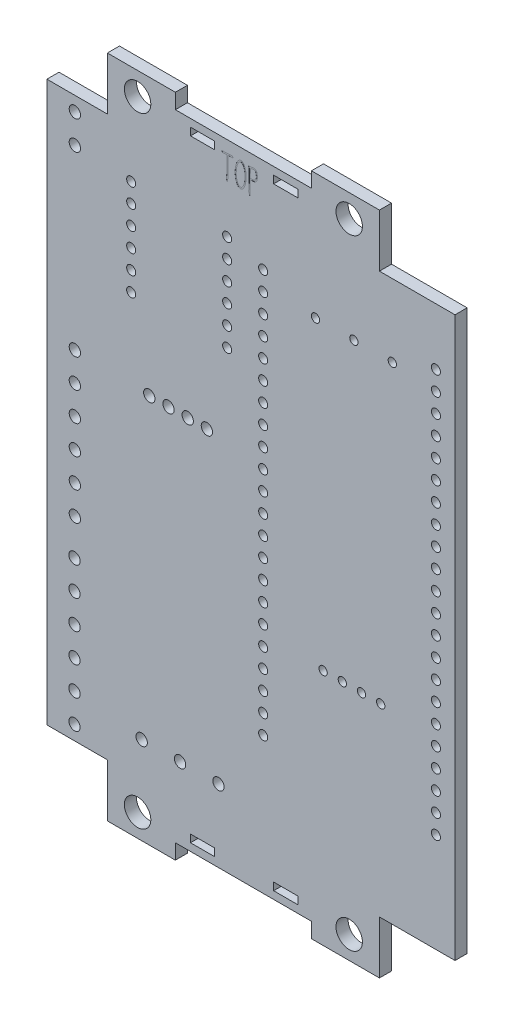
SolidWorks part; units mm, degrees
ref_plane "前视基准面" through (0, 0, 0) normal (0, 0, 1) x (1, 0, 0)
ref_plane "上视基准面" through (0, 0, 0) normal (0, 1, 0) x (1, 0, 0)
ref_plane "右视基准面" through (0, 0, 0) normal (1, 0, 0) x (0, 0, -1)
sketch "草图1" plane through (0, 0, 0) normal (0, 0, 1) x (1, 0, 0)
  line L1 (0, 0) -> (54, 0)
  line L2 (0, 0) -> (0, 88)
  line L3 (0, 88) -> (54, 88)
  line L4 (54, 0) -> (54, 88)
  dimension "D1" = 88
  dimension "D2" = 54
extrude "凸台-拉伸1" add sketch "草图1" along normal blind 1.6
sketch "草图2" plane through (0, 0, 1.6) normal (0, 0, 1) x (1, 0, 0)
  line L0 (26, 88) -> (26, -11.2247) construction
  line L2 (0, 44) -> (77.0225, 44) construction
  line L3 (0, 88) -> (0, 0) construction
  circle A0 centre (12, 85) radius 1.75
  circle A1 centre (40, 85) radius 1.75
  circle A2 centre (12, 3) radius 1.75
  circle A3 centre (40, 3) radius 1.75
  dimension "D1" = 28
  dimension "D2" = 82
  dimension "D3" = 3.5
  dimension "D4" = 12
extrude "切除-拉伸1" cut sketch "草图2" against normal blind 10
sketch "草图3" plane through (0, 0, 0) normal (0, 0, -1) x (-1, 0, 0)
  circle A0 centre (-51.476, 73.476) radius 0.6
  circle A1 centre (-28.616, 73.476) radius 0.6
  dimension "D1" = 1.2
extrude "切除-拉伸2" cut sketch "草图3" against normal blind 10
pattern_linear "阵列(线性)1" count 22 spacing 2.54 along (0, -1, 0) of "切除-拉伸2"
sketch "草图4" plane through (0, 0, 0) normal (0, 0, -1) x (-1, 0, 0)
  circle A0 centre (-3.7, 51.815) radius 0.75
  circle A1 centre (-3.6518, 27.955) radius 0.75
  dimension "D1" = 1.5
extrude "切除-拉伸3" cut sketch "草图4" against normal blind 10
pattern_linear "阵列(线性)2" count 6 spacing 3.81 along (0, -1, 0) of "切除-拉伸3"
sketch "草图5" plane through (0, 0, 0) normal (0, 0, -1) x (-1, 0, 0)
  circle A0 centre (-3.7, 79.095) radius 0.75
  dimension "D1" = 1.5
extrude "切除-拉伸4" cut sketch "草图5" against normal blind 10
pattern_linear "阵列(线性)3" count 2 spacing 3.81 along (0, -1, 0) of "切除-拉伸4"
sketch "草图6" plane through (0, 0, 1.6) normal (0, 0, 1) x (1, 0, 0)
  circle A0 centre (11.15, 74.85) radius 0.6
  circle A1 centre (23.85, 74.85) radius 0.6
  dimension "D1" = 1.2
extrude "切除-拉伸5" cut sketch "草图6" against normal blind 10
pattern_linear "阵列(线性)4" count 6 spacing 2.54 along (0, -1, 0) of "切除-拉伸5"
sketch "草图7" plane through (0, 0, 1.6) normal (0, 0, 1) x (1, 0, 0)
  line L1 (0, 88) -> (8, 88)
  line L2 (0, 88) -> (0, 81)
  line L3 (0, 81) -> (8, 81)
  line L4 (8, 88) -> (8, 81)
  line L5 (54, 88) -> (44, 88)
  line L6 (54, 88) -> (54, 81)
  line L7 (54, 81) -> (44, 81)
  line L8 (44, 88) -> (44, 81)
  line L9 (0, 0) -> (8, 0)
  line L10 (0, 0) -> (0, 7)
  line L11 (0, 7) -> (8, 7)
  line L12 (8, 0) -> (8, 7)
  line L13 (54, 0) -> (44, 0)
  line L14 (54, 0) -> (54, 7)
  line L15 (54, 7) -> (44, 7)
  line L16 (44, 0) -> (44, 7)
  dimension "D1" = 8
  dimension "D2" = 7
  dimension "D3" = 10
  dimension "D4" = 7
  dimension "D5" = 8
  dimension "D6" = 7
  dimension "D7" = 10
  dimension "D8" = 7
extrude "切除-拉伸6" cut sketch "草图7" against normal blind 10
sketch "草图8" plane through (0, 0, 0) normal (0, 0, -1) x (-1, 0, 0)
  circle A0 centre (-45.7, 71.4) radius 0.55
  circle A1 centre (-40.62, 71.4) radius 0.55
  circle A2 centre (-35.54, 71.4) radius 0.55
  circle A3 centre (-44.17, 31.5) radius 0.55
  circle A4 centre (-41.63, 31.5) radius 0.55
  circle A5 centre (-39.09, 31.5) radius 0.55
  circle A6 centre (-36.55, 31.5) radius 0.55
  dimension "D1" = 1.1
extrude "切除-拉伸7" cut sketch "草图8" against normal blind 10
sketch "草图9" plane through (0, 0, 1.6) normal (0, 0, 1) x (1, 0, 0)
  circle A0 centre (13.55, 51.5) radius 0.75
  circle A1 centre (16.09, 51.5) radius 0.75
  circle A2 centre (18.63, 51.5) radius 0.75
  circle A3 centre (21.17, 51.5) radius 0.75
  circle A4 centre (12.54, 11.6) radius 0.75
  circle A5 centre (17.62, 11.6) radius 0.75
  circle A6 centre (22.7, 11.6) radius 0.75
  dimension "D1" = 1.5
extrude "切除-拉伸8" cut sketch "草图9" against normal blind 10
sketch "草图10" plane through (0, 0, 0) normal (0, -1, 0) x (1, 0, 0)
  line L0 (8, 1.6) -> (44, 1.6) construction
  line L1 (17, 1.6) -> (35, 1.6)
  line L2 (17, 1.6) -> (17, 0)
  line L3 (17, 0) -> (35, 0)
  line L4 (35, 1.6) -> (35, 0)
  line L5 (8, 0) -> (44, 0) construction
  line L6 (8, 0) -> (8, 1.6) construction
  line L7 (44, 0) -> (44, 1.6) construction
  dimension "D1" = 9
  dimension "D2" = 9
extrude "切除-拉伸9" cut sketch "草图10" against normal blind 2
ref_plane "基准面1" through (0, 44, 0) normal (0, -1, 0) x (-1, 0, 0)
mirror "镜向1" about plane through (0, 44, 0) normal (0, -1, 0) of "切除-拉伸9"
sketch "草图11" plane through (0, 0, 1.6) normal (0, 0, 1) x (1, 0, 0)
  text T0 "TOP"
extrude "切除-拉伸10" cut sketch "草图11" against normal blind 0.01
sketch "草图12" plane through (0, 0, 0) normal (0, 0, -1) x (-1, 0, 0)
  line L1 (-33.2, 85) -> (-30, 85)
  line L2 (-33.2, 85) -> (-33.2, 84)
  line L3 (-33.2, 84) -> (-30, 84)
  line L4 (-30, 85) -> (-30, 84)
  line L5 (-22.2, 85) -> (-19, 85)
  line L6 (-22.2, 85) -> (-22.2, 84)
  line L7 (-22.2, 84) -> (-19, 84)
  line L8 (-19, 85) -> (-19, 84)
  line L9 (-33.2, 4) -> (-30, 4)
  line L10 (-33.2, 4) -> (-33.2, 3)
  line L11 (-33.2, 3) -> (-30, 3)
  line L12 (-30, 4) -> (-30, 3)
  line L13 (-22.2, 4) -> (-19, 4)
  line L14 (-22.2, 4) -> (-22.2, 3)
  line L15 (-22.2, 3) -> (-19, 3)
  line L16 (-19, 4) -> (-19, 3)
extrude "切除-拉伸11" cut sketch "草图12" against normal through all
sketch "草图13" plane through (0, 0, 0) normal (0, 0, -1) x (-1, 0, 0)
  text T0 "S1" font "汉仪长仿宋体" height in points 6
extrude "切除-拉伸12" cut sketch "草图13" against normal blind 0.01
sketch "草图14" plane through (0, 0, 0) normal (0, 0, -1) x (-1, 0, 0)
  text T0 "S2" font "汉仪长仿宋体" height in points 6
extrude "切除-拉伸13" cut sketch "草图14" against normal blind 0.01
sketch "草图15" plane through (0, 0, 0) normal (0, 0, -1) x (-1, 0, 0)
  text T0 "PWR" font "汉仪长仿宋体" height in points 6
extrude "切除-拉伸14" cut sketch "草图15" against normal blind 0.01
sketch "草图16" plane through (0, 0, 0) normal (0, 0, -1) x (-1, 0, 0)
  text T0 "DATA" font "汉仪长仿宋体" height in points 6
extrude "切除-拉伸15" cut sketch "草图16" against normal blind 0.01
sketch "草图17" plane through (0, 0, 0) normal (0, 0, -1) x (-1, 0, 0)
  line L0 (-54, 7) -> (-54, 81) construction
  line L1 (-44, 16) -> (-36, 16)
  line L2 (-44, 16) -> (-44, 8)
  line L3 (-44, 8) -> (-36, 8)
  line L4 (-36, 16) -> (-36, 8)
  line L5 (-35, 0) -> (-44, 0) construction
  dimension "D1" = 8
  dimension "D2" = 8
  dimension "D3" = 10
  dimension "D4" = 8
extrude "凸台-拉伸2" add sketch "草图17" along normal blind 4.5
